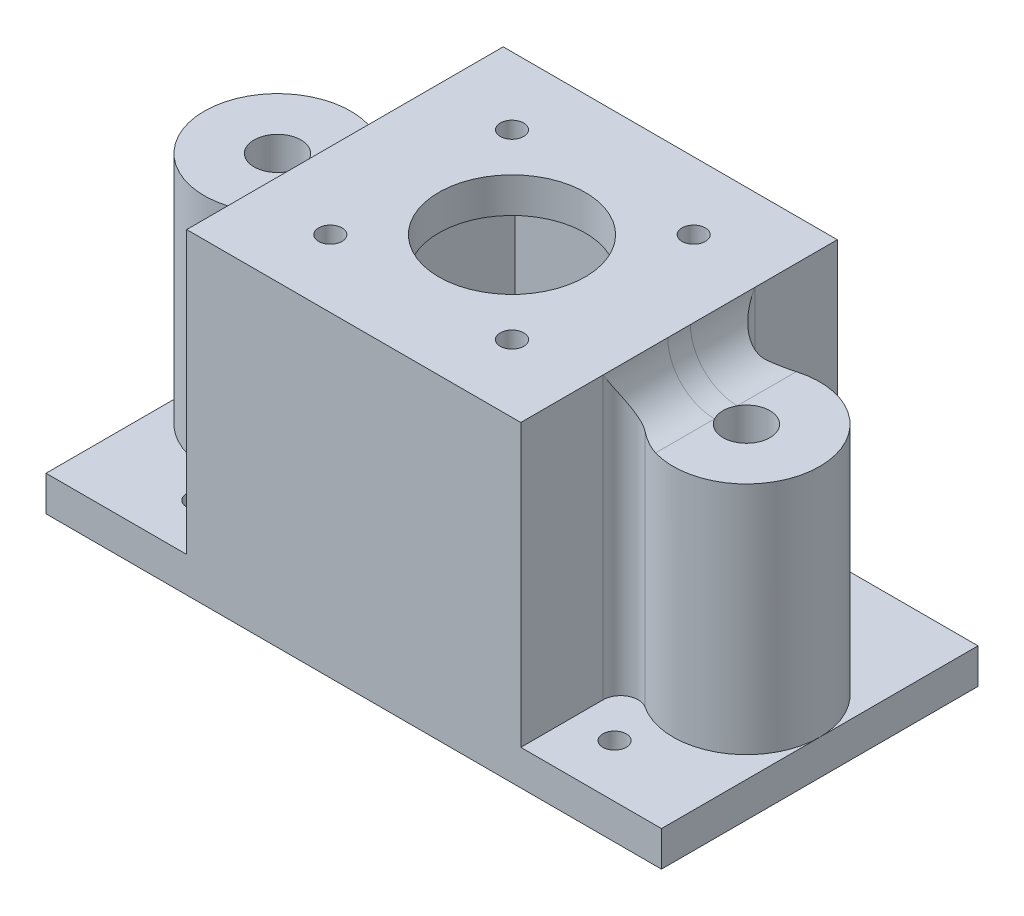
SolidWorks part; units mm, degrees
material "ABS"
ref_plane "Plano frontal" through (0, 0, 0) normal (0, 0, 1) x (1, 0, 0)
ref_plane "Plano superior" through (0, 0, 0) normal (0, 1, 0) x (1, 0, 0)
ref_plane "Plano direito" through (0, 0, 0) normal (1, 0, 0) x (0, 0, -1)
sketch "Esboço1" plane through (0, 0, 0) normal (0, 0, 1) x (1, 0, 0)
  line L0 (-28.5, 54) -> (28.5, 54)
  line L1 (28.5, 54) -> (28.5, 6)
  line L2 (52.5, 6) -> (28.5, 6)
  line L3 (52.5, 6) -> (52.5, 0)
  line L4 (52.5, 0) -> (22.5, 0)
  line L5 (22.5, 0) -> (22.5, 48)
  line L6 (22.5, 48) -> (-22.5, 48)
  line L7 (28.5, 6) -> (22.5, 6) construction
  line L8 (22.5, 48) -> (22.5, 54) construction
  line L9 (0, 63.425) -> (0, 0) construction
  line L10 (-22.5, 48) -> (-22.5, 54) construction
  line L11 (-28.5, 6) -> (-22.5, 6) construction
  line L12 (-22.5, 0) -> (-22.5, 48)
  line L13 (-52.5, 0) -> (-22.5, 0)
  line L14 (-52.5, 6) -> (-52.5, 0)
  line L15 (-52.5, 6) -> (-28.5, 6)
  line L16 (-28.5, 54) -> (-28.5, 6)
  point P19 (0, 48)
  point P23 (0, 54)
  dimension "D1" = 48
  dimension "D2" = 6
  dimension "D3" = 45
  dimension "D4" = 105
extrude "Ressalto-extrusão1" add sketch "Esboço1" along normal mid plane 54
sketch "Esboço2" plane through (0, 54, 0) normal (0, 1, 0) x (1, 0, 0)
  line L0 (0, 27) -> (0, -27) construction
  line L1 (28.5, 27) -> (-28.5, 27) construction
  line L2 (28.5, -27) -> (-28.5, -27) construction
  line L4 (-15.5, 15.5) -> (15.5, 15.5) construction
  line L5 (-15.5, 15.5) -> (-15.5, -15.5) construction
  line L6 (-15.5, -15.5) -> (15.5, -15.5) construction
  line L7 (15.5, 15.5) -> (15.5, -15.5) construction
  line L8 (-15.5, 15.5) -> (15.5, -15.5) construction
  line L9 (-15.5, -15.5) -> (15.5, 15.5) construction
  circle A0 centre (0, 0) radius 12.5
  circle A1 centre (-15.5, 15.5) radius 2
  circle A2 centre (15.5, 15.5) radius 2
  circle A3 centre (15.5, -15.5) radius 2
  circle A4 centre (-15.5, -15.5) radius 2
  dimension "D1" = 4
  dimension "D3" = 25
  dimension "D2" = 31
extrude "Corte-extrusão1" cut sketch "Esboço2" against normal blind 42
sketch "Esboço3" plane through (0, 6, 0) normal (0, 1, 0) x (1, 0, 0)
  line L0 (27.7526, 2.5) -> (28.5, 2.5)
  line L2 (0, 35.3204) -> (0, -32.8451) construction
  line L3 (0, 0) -> (71.2121, 0) construction
  line L4 (27.7526, -2.5) -> (28.5, -2.5)
  line L6 (28.5, -2.5) -> (28.5, 2.5)
  line L7 (-27.7526, -2.5) -> (-28.5, -2.5)
  line L8 (-28.5, -2.5) -> (-28.5, 2.5)
  line L9 (-27.7526, 2.5) -> (-28.5, 2.5)
  line L10 (28.5, -27) -> (28.5, 27) construction
  arc A0 (27.7526, -2.5) -> (27.7526, 2.5) centre (40, 0) ccw
  circle A1 centre (40, 0) radius 4
  circle A2 centre (-40, 0) radius 4
  arc A3 (-27.7526, -2.5) -> (-27.7526, 2.5) centre (-40, 0) cw
  dimension "D2" = 25
  dimension "D3" = 8
  dimension "D1" = 5
  dimension "D4" = 40
extrude "Ressalto-extrusão2" add sketch "Esboço3" along normal blind 40
fillet "Filete1" radius 8 2 edges at (-28.5, 46, 0) (28.5, 46, 0)
sketch "Esboço4" plane through (0, 6, 0) normal (0, 1, 0) x (1, 0, 0)
  line L0 (-35.5, 18) -> (-35.5, 27) construction
  line L1 (-28.5, 27) -> (-52.5, 27) construction
  line L2 (-35.5, 18) -> (-52.5, 18) construction
  line L3 (-52.5, -27) -> (-52.5, 0) construction
  line L4 (-59.6325, 0) -> (0, 0) construction
  line L5 (0, 0) -> (0, 35.3341) construction
  circle A0 centre (-35.5, 18) radius 2
  circle A1 centre (-35.5, 18) radius 5.5 construction
  circle A2 centre (35.5, 18) radius 2
  circle A3 centre (35.5, -18) radius 2
  circle A4 centre (-35.5, -18) radius 2
  dimension "D1" = 4
  dimension "D2" = 11
  dimension "D3" = 9
  dimension "D4" = 17
extrude "Corte-extrusão2" cut sketch "Esboço4" against normal through all
fillet "Filete5" radius 3 4 edges at (-28.5, 30, -4.899) (-28.5, 30, 4.899) (28.5, 30, -4.899) (28.5, 30, 4.899)
sketch "Esboço5" plane through (0, 0, 0) normal (0, -1, 0) x (1, 0, 0)
  line L0 (-22.5, 27) -> (22.5, 27)
  line L1 (22.5, 27) -> (22.5, 23)
  line L2 (22.5, 27) -> (22.5, -27) construction
  line L3 (22.5, 23) -> (-22.5, 23)
  line L4 (-22.5, 27) -> (-22.5, -27) construction
  line L5 (-22.5, 23) -> (-22.5, 27)
  line L6 (-22.5, 0) -> (25.9689, 0) construction
  line L7 (-22.5, 27) -> (-22.5, -27) construction
  line L8 (-22.5, -23) -> (-22.5, -27)
  line L9 (22.5, -23) -> (-22.5, -23)
  line L10 (22.5, -27) -> (22.5, -23)
  line L11 (-22.5, -27) -> (22.5, -27)
  dimension "D1" = 4
extrude "Ressalto-extrusão3" add sketch "Esboço5" against normal up to surface (48 mm away) up to face at (-15.5, 48, -13.5)
sketch "Esboço6" plane through (0, 0, -27) normal (0, 0, -1) x (-1, 0, 0)
  line L0 (52.5, 0) -> (-52.5, 0) construction
  line L1 (-10, 0) -> (10, 0)
  line L2 (-10, 0) -> (-10, 15)
  line L3 (-10, 15) -> (10, 15)
  line L4 (10, 0) -> (10, 15)
  point P6 (-1.014, 0)
  point P7 (0, 0)
  point P8 (0, 0)
  dimension "D1" = 20
  dimension "D2" = 15
extrude "Corte-extrusão3" cut sketch "Esboço6" against normal blind 10
